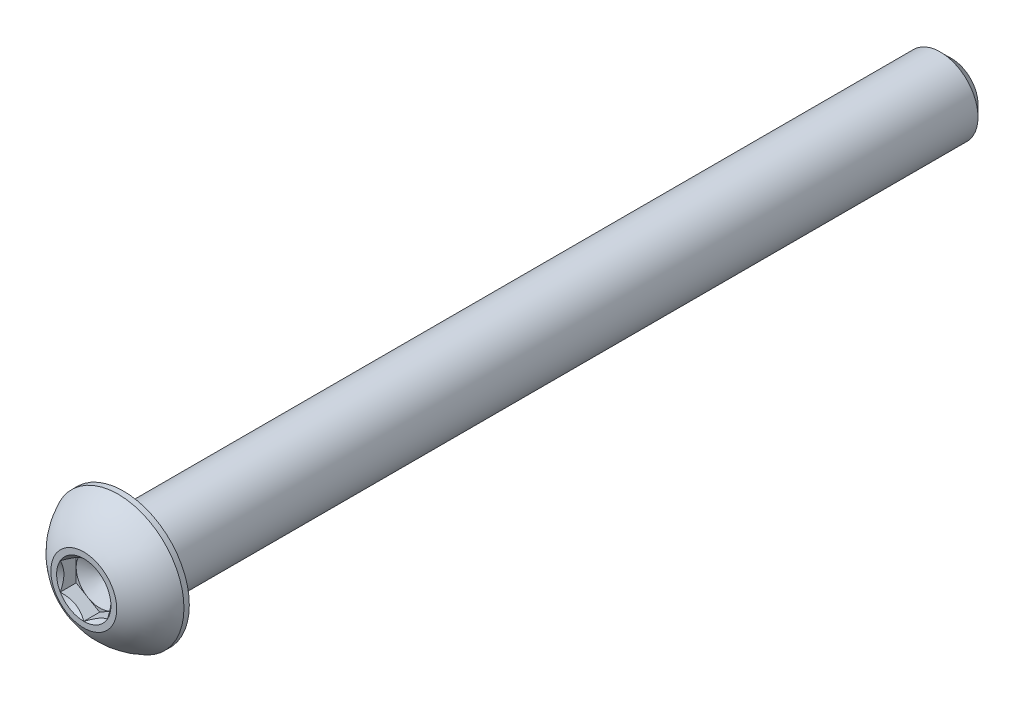
SolidWorks part; units mm, degrees
material "Plain Carbon Steel"
ref_plane "Front Plane" through (0, 0, 0) normal (0, 0, 1) x (1, 0, 0)
ref_plane "Top Plane" through (0, 0, 0) normal (0, 1, 0) x (1, 0, 0)
ref_plane "Right Plane" through (0, 0, 0) normal (1, 0, 0) x (0, 0, -1)
sketch "Sketch1" plane through (0, 0, 0) normal (1, 0, 0) x (0, 0, -1)
  line L0 (-36.6014, 0) -> (36.6014, 0) construction
  line L1 (-33.2486, 5.5499) -> (-33.2486, -5.5499) construction
  line L2 (-36.6014, 1.9844) -> (-36.6014, -1.9844) construction
  line L3 (36.6014, 3.175) -> (36.6014, -3.175) construction
  line L4 (36.522, 3.3125) -> (37.157, 2.2126) construction
  line L5 (37.157, 2.2126) -> (37.792, 3.3125) construction
  line L6 (37.792, 3.3125) -> (36.522, 3.3125) construction
  line L7 (37.157, 3.3125) -> (37.157, 3.175) construction
  line L8 (37.157, 2.2126) -> (37.157, 2.3501) construction
  line L9 (37.0776, 2.3501) -> (37.2364, 2.3501)
  line L10 (-36.6014, 2.7781) -> (-36.6014, -2.7781) construction
  line L11 (-33.2486, 5.5499) -> (-33.7022, 5.5499) construction
  line L12 (-36.6014, 1.9844) -> (-35.2603, 1.9844) construction
  line L13 (-35.2603, 1.9844) -> (-34.1146, 0) construction
  point P5 (-33.2486, 0)
  point P10 (30.8864, -3.175)
  point P21 (11.2014, 3.175)
  dimension "Drive Size" = 3.9688
  dimension "Head Diameter" = 11.0998
  dimension "Head Height" = 3.3528
  dimension "Diameter" = 6.35
  dimension "Thread Length" = 69.85
  dimension "D1" = 5.715
  dimension "Pitch" = 1.27
  dimension "D2" = 0.1588
  dimension "D3" = 5.5563
  dimension "D4" = 0.4536
  dimension "D5" = 60
  dimension "D6" = 1.3411
  dimension "Partially Threaded" = 25.4
sketch "Sketch2" plane through (0, 0, 0) normal (1, 0, 0) x (0, 0, -1)
  line L0 (-36.6014, 1.9844) -> (-36.6014, 2.7781)
  line L1 (-33.7022, 5.5499) -> (-33.2486, 5.5499)
  line L2 (-33.2486, 5.5499) -> (-33.2486, 3.175)
  line L3 (-33.2486, 5.5499) -> (-33.2486, -5.5499) construction
  line L4 (-33.2486, 3.175) -> (35.6489, 3.175)
  line L5 (36.6014, 2.2225) -> (36.6014, 0)
  line L6 (-36.6014, 1.9844) -> (-35.2603, 1.9844)
  line L7 (-35.2603, 1.9844) -> (-34.1146, 0)
  line L8 (36.6014, 0) -> (-34.1146, 0)
  line L9 (35.6489, 3.175) -> (36.6014, 2.2225)
  arc A0 (-33.7022, 5.5499) -> (-36.6014, 2.7781) centre (-31.1708, 0) ccw
  point P13 (36.6014, 3.175)
  dimension "D1" = 0.9525
  dimension "D2" = 45
revolve "Revolve1" add sketch "Sketch2" angle 360 about L0
sketch "Sketch3" plane through (0, 0, 0) normal (0, 0, 1) x (1, 0, 0)
  line L1 (0, 2.2914) -> (-1.9844, 1.1457)
  line L2 (-1.9844, 1.1457) -> (-1.9844, -1.1457)
  line L3 (-1.9844, -1.1457) -> (0, -2.2914)
  line L4 (0, -2.2914) -> (1.9844, -1.1457)
  line L5 (1.9844, -1.1457) -> (1.9844, 1.1457)
  line L6 (1.9844, 1.1457) -> (0, 2.2914)
  circle A0 centre (0, 0) radius 1.9844 construction
extrude "Cut-Extrude1" cut sketch "Sketch3" along normal through all from vertex starting at point (0, 1.9844, 35.2603)
sketch "Sketch4" plane through (0, 0, 36.6014) normal (0, 0, 1) x (1, 0, 0)
  circle A0 centre (0, 0) radius 2.2914
extrude "Cut-Extrude2" cut sketch "Sketch4" against normal up to next (73.2028 mm away) draft 45
ref_axis "Center Axis 1" [suppressed] through (0, 0, -38.3654) along (0, 0, 1)
ref_plane "Contact Plane 1" [suppressed] through (0, 0, 29.2227) normal (0, 0, -1) x (-1, 0, 0)
equation "\"D2@Sketch1\"=\"Pitch@Sketch1\"*.125"
equation "\"D1@Sketch1\"=\"Pitch@Sketch1\"*4.5"
equation "\"D3@Sketch1\"=\"Drive Size@Sketch1\"*1.4"
equation "\"D4@Sketch1\"=(\"D3@Sketch1\"-\"Drive Size@Sketch1\")/3.5"
equation "\"D6@Sketch1\"=\"Head Height@Sketch1\"*.40"
equation "\"D1@Sketch2\"=\"Pitch@Sketch1\"*.750"
